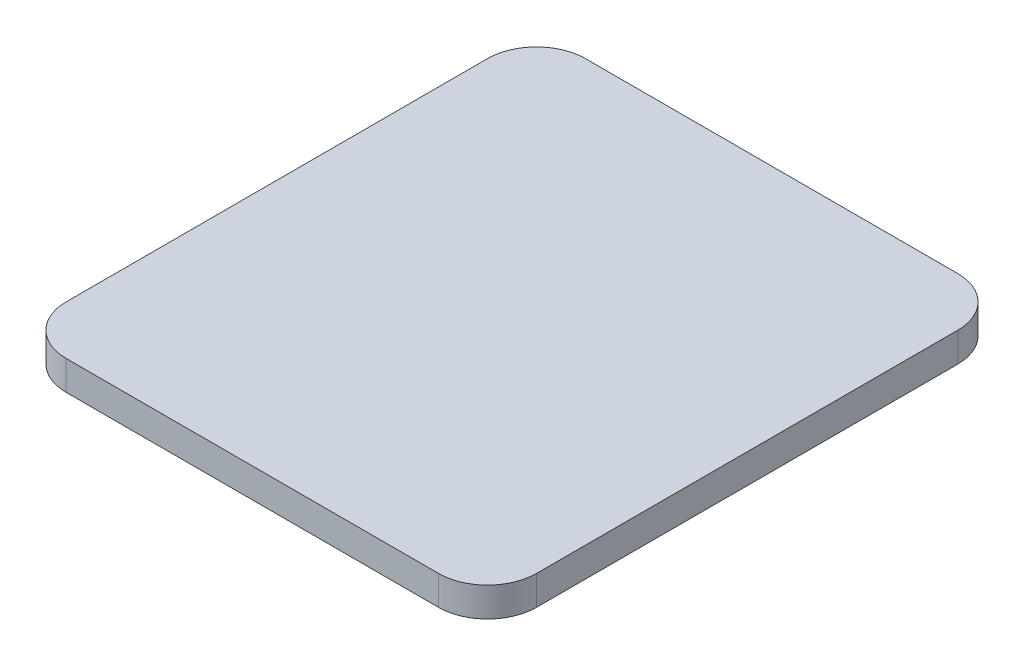
SolidWorks part; units mm, degrees
ref_plane "Front Plane" through (0, 0, 0) normal (0, 0, 1) x (1, 0, 0)
ref_plane "Top Plane" through (0, 0, 0) normal (0, 1, 0) x (1, 0, 0)
ref_plane "Right Plane" through (0, 0, 0) normal (1, 0, 0) x (0, 0, -1)
sketch "Sketch1" plane through (0, 29.1718, 0) normal (0, -1, 0) x (1, 0, 0)
  line L8 (13.9215, 29.7805) -> (51.9215, 29.7805)
  line L9 (56.9215, 34.7805) -> (56.9215, 77.7805)
  line L10 (51.9215, 82.7805) -> (13.9215, 82.7805)
  line L11 (8.9215, 77.7805) -> (8.9215, 34.7805)
  line L12 (13.9215, 29.7805) -> (51.9215, 29.7805)
  line L13 (56.9215, 34.7805) -> (56.9215, 77.7805)
  line L14 (51.9215, 82.7805) -> (13.9215, 82.7805)
  line L15 (8.9215, 77.7805) -> (8.9215, 34.7805)
  arc A8 (8.9215, 34.7805) -> (13.9215, 29.7805) centre (13.9215, 34.7805) ccw
  arc A9 (51.9215, 29.7805) -> (56.9215, 34.7805) centre (51.9215, 34.7805) ccw
  arc A10 (56.9215, 77.7805) -> (51.9215, 82.7805) centre (51.9215, 77.7805) ccw
  arc A11 (13.9215, 82.7805) -> (8.9215, 77.7805) centre (13.9215, 77.7805) ccw
  arc A12 (8.9215, 34.7805) -> (13.9215, 29.7805) centre (13.9215, 34.7805) ccw
  arc A13 (51.9215, 29.7805) -> (56.9215, 34.7805) centre (51.9215, 34.7805) ccw
  arc A14 (56.9215, 77.7805) -> (51.9215, 82.7805) centre (51.9215, 77.7805) ccw
  arc A15 (13.9215, 82.7805) -> (8.9215, 77.7805) centre (13.9215, 77.7805) ccw
  dimension "D1" = 0
extrude "Boss-Extrude1" add sketch "Sketch1" along normal blind 3
